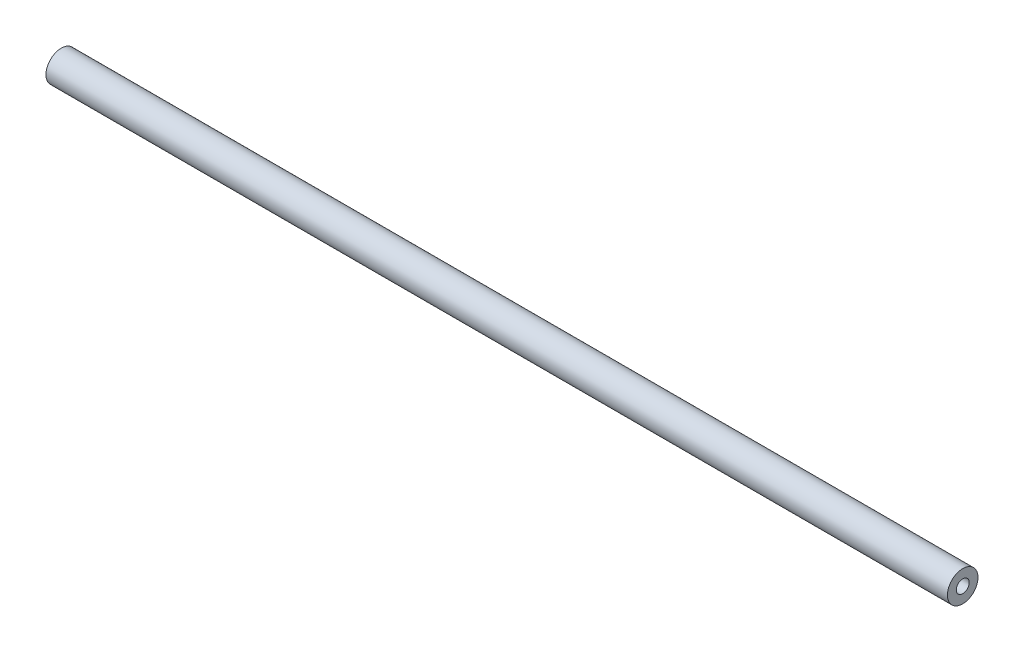
SolidWorks part; units mm, degrees
material "7075-T6 (SN)"
ref_plane "Front Plane" through (0, 0, 0) normal (0, 0, 1) x (1, 0, 0)
ref_plane "Top Plane" through (0, 0, 0) normal (0, 1, 0) x (1, 0, 0)
ref_plane "Right Plane" through (0, 0, 0) normal (1, 0, 0) x (0, 0, -1)
sketch "Sketch1" plane through (0, 0, 0) normal (1, 0, 0) x (0, 0, -1)
  circle A1 centre (0, 0) radius 4.7625
  dimension "D1" = 9.525
extrude "Boss-Extrude1" add sketch "Sketch1" along normal mid plane 280.9875 contours A1 region at (0, 0, 0)
hole_wizard "#10-32 Tapped Hole1" positions "3DSketch1" profile "Sketch2" tap size "#10-32" standard "ANSI Inch"
sketch3d "3DSketch1"
  line L0 (140.4938, 0, 0) -> (-140.4938, 0, 0) construction
  point P0 (140.4938, 0, 0)
  point P7 (-140.4938, 0, 0)
sketch "Sketch2" plane through (140.4938, 0, 0) normal (0, 1, 0) x (0, 0, -1)
  line L0 (0, 0) -> (0, 13.2428)
  line L1 (0, 13.2428) -> (2.0193, 12.0294)
  line L2 (2.0193, 12.0294) -> (2.0193, 0)
  line L5 (2.0193, 0) -> (0, 0)
  line L10 (0, 13.2428) -> (-2.0193, 12.0294) construction
  line L11 (0, -6.35) -> (0, 107.95) construction
  dimension "Tap Drill Dia." = 4.0386
  dimension "Tap Drill Depth" = 12.0294
  dimension "Drill Angle" = 118
cosmetic thread "Hole Thread1"
cosmetic thread "Hole Thread2"
